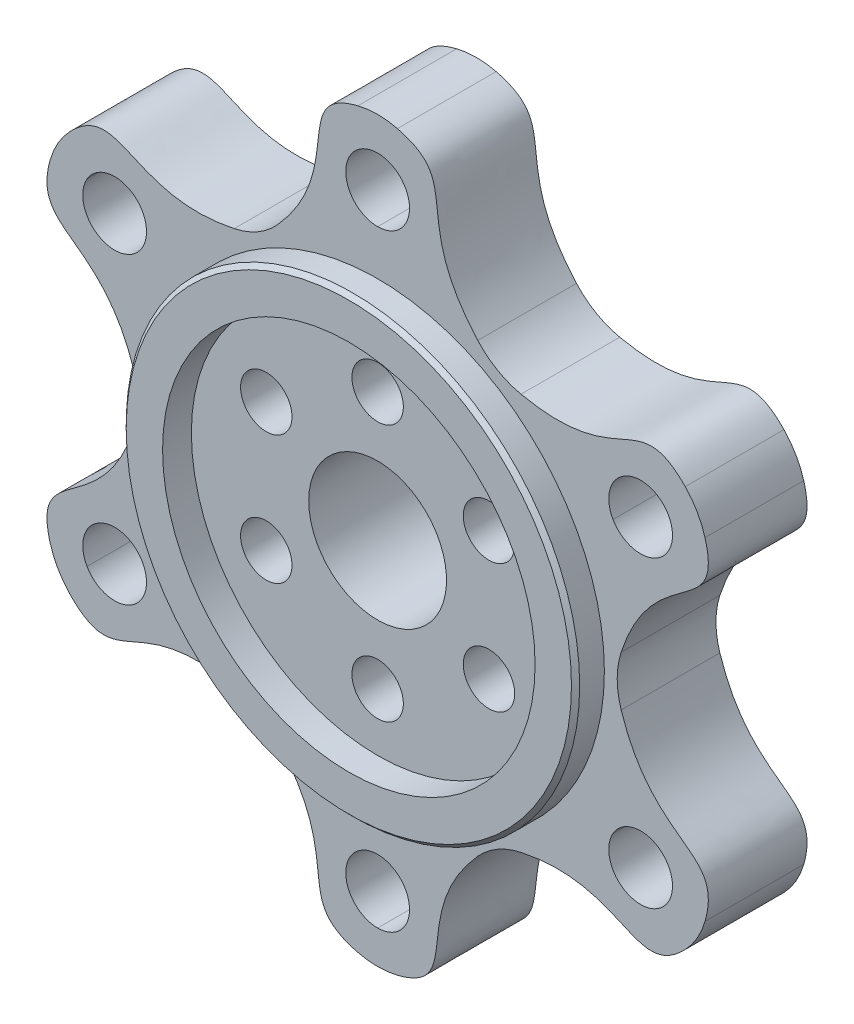
SolidWorks part; units mm, degrees
ref_plane "Front Plane" through (0, 0, 0) normal (0, 0, 1) x (1, 0, 0)
ref_plane "Top Plane" through (0, 0, 0) normal (0, 1, 0) x (1, 0, 0)
ref_plane "Right Plane" through (0, 0, 0) normal (1, 0, 0) x (0, 0, -1)
sketch "Sketch1" plane through (0, 0, 0) normal (0, 0, 1) x (1, 0, 0)
  line L0 (0, -55) -> (0, 55) construction
  line L1 (0, 0) -> (0, 45.72) construction
  circle A0 centre (0, 0) radius 8.509
  circle A1 centre (0, 0) radius 45.72
  circle A2 centre (0, 15.875) radius 3.175
  circle A3 centre (13.7482, 7.9375) radius 3.175
  circle A4 centre (13.7482, -7.9375) radius 3.175
  circle A5 centre (0, -15.875) radius 3.175
  circle A6 centre (-13.7482, -7.9375) radius 3.175
  circle A7 centre (-13.7482, 7.9375) radius 3.175
  circle A8 centre (0, 37.5) radius 3.937
  circle A10 centre (32.476, 18.75) radius 3.937
  circle A11 centre (32.476, -18.75) radius 3.937
  circle A12 centre (0, -37.5) radius 3.937
  circle A13 centre (-32.476, -18.75) radius 3.937
  circle A14 centre (-32.476, 18.75) radius 3.937
  point P21 (0, 0)
  point P36 (0, 0)
  dimension "D1" = 17.018
  dimension "D2" = 91.44
  dimension "D3" = 6.35
  dimension "D6" = 7.874
  dimension "D4" = 15.875
  dimension "D8" = 37.5
  dimension "D5" = 6
  dimension "D7" = 6
extrude "Boss-Extrude3" add sketch "Sketch1" along normal blind 12.192
sketch "Sketch2" plane through (0, 0, 12.192) normal (0, 0, 1) x (1, 0, 0)
  line L0 (0, -55) -> (0, 55) construction
  line L1 (-32.476, 18.75) -> (0, 37.5) construction
  line L2 (-16.238, 28.125) -> (-4.2545, 7.369) construction
  line L3 (16.1981, 28.148) -> (4.2146, 7.3919) construction
  line L6 (32.476, -18.75) -> (32.476, 18.75) construction
  line L7 (32.476, 18.75) -> (0, 37.5) construction
  line L8 (55, 0) -> (-55, 0) construction
  circle A0 centre (0, 0) radius 27.94 construction
  circle A1 centre (0, 0) radius 45.72 construction
  circle A2 centre (0, 0) radius 8.509 construction
  circle A3 centre (0, 0) radius 45.72
  spline S0 degree 3 poles (-14.625, 25.3312) (-1.5745, 37.1177) (-13.1193, 43.9586) (0, 45.72) knots 0 0 0 0 1 1 1 1
  spline S1 degree 3 poles (14.625, 25.3312) (1.5745, 37.1177) (13.1193, 43.9586) (0, 45.72) knots 0 0 0 0 1 1 1 1
  spline S2 degree 3 poles (-29.25, 0) (-32.9321, 17.1953) (-44.6289, 10.6177) (-39.5947, 22.86) knots 0 0 0 0 1 1 1 1
  spline S3 degree 3 poles (-14.625, 25.3312) (-31.3576, 19.9224) (-31.5096, 33.3409) (-39.5947, 22.86) knots 0 0 0 0 1 1 1 1
  spline S4 degree 3 poles (-14.625, -25.3312) (-31.3576, -19.9224) (-31.5096, -33.3409) (-39.5947, -22.86) knots 0 0 0 0 1 1 1 1
  spline S5 degree 3 poles (-29.25, 0) (-32.9321, -17.1953) (-44.6289, -10.6177) (-39.5947, -22.86) knots 0 0 0 0 1 1 1 1
  spline S6 degree 3 poles (14.625, -25.3312) (31.3576, -19.9224) (31.5096, -33.3409) (39.5947, -22.86) knots 0 0 0 0 1 1 1 1
  spline S7 degree 3 poles (29.25, 0) (32.9321, -17.1953) (44.6289, -10.6177) (39.5947, -22.86) knots 0 0 0 0 1 1 1 1
  spline S8 degree 3 poles (14.625, -25.3312) (1.5745, -37.1177) (13.1193, -43.9586) (0, -45.72) knots 0 0 0 0 1 1 1 1
  spline S9 degree 3 poles (-14.625, -25.3312) (-1.5745, -37.1177) (-13.1193, -43.9586) (0, -45.72) knots 0 0 0 0 1 1 1 1
  spline S10 degree 3 poles (29.25, 0) (32.9321, 17.1953) (44.6289, 10.6177) (39.5947, 22.86) knots 0 0 0 0 1 1 1 1
  spline S11 degree 3 poles (14.625, 25.3312) (31.3576, 19.9224) (31.5096, 33.3409) (39.5947, 22.86) knots 0 0 0 0 1 1 1 1
  point P5 (-16.238, 28.125)
  point P6 (16.1981, 28.148)
  circle M8 centre (0, 0) radius 45.72
  dimension "D1" = 55.88
  dimension "D2" = 18.796
  dimension "D3" = 29.25
extrude "Cut-Extrude1" cut sketch "Sketch2" against normal blind 22.86 contours S1 S11 M8 | S5 S2 A3 | S10 S7 A3 | S6 S8 A3 | S9 S4 M8 | S3 S0 M8 region at (38.672, 0, 12.192) region at (19.336, 33.4909, 12.192) region at (19.336, -33.4909, 12.192) region at (-19.336, 33.4909, 12.192) region at (-19.336, -33.4909, 12.192) region at (-38.672, 0, 12.192)
sketch "Sketch4" plane through (0, 0, 12.192) normal (0, 0, 1) x (1, 0, 0)
  circle A0 centre (0, 0) radius 8.509 construction
  circle A1 centre (0, 0) radius 8.509 construction
  circle A2 centre (0, 0) radius 28
  circle A3 centre (0, 0) radius 23
  dimension "D1" = 56
  dimension "D2" = 46
extrude "Boss-Extrude4" add sketch "Sketch4" along normal blind 3.556 contours A2 | A3
ref_plane "Plane1" through (0, 0, 0) normal (1, 0, 0) x (0, 0, -1)
ref_plane "Plane2" through (0, 0, 0) normal (-0.5, -0.866, 0) x (-0.866, 0.5, 0)
ref_plane "Plane3" through (0, 0, 0) normal (-0.5, 0.866, 0) x (0.866, 0.5, 0)
split line "Split Line1"
split line "Split Line2"
split line "Split Line3"
ref_axis "Axis1" through (0, 0, 12.192) along (0, 0, -1)
fillet "Fillet1" radius 10 12 edges at (29.25, 0, 6.096) (39.5947, -22.86, 6.096) (0, -45.72, 6.096) (14.625, -25.3312, 6.096) (-14.625, -25.3312, 6.096) (-39.5947, -22.86, 6.096) (-29.25, 0, 6.096) (-39.5947, 22.86, 6.096) (-14.625, 25.3312, 6.096) (14.625, 25.3312, 6.096) (39.5947, 22.86, 6.096) (0, 45.72, 6.096)
chamfer "Chamfer1" distance 0.508 angle 45 1 edges at (28, 0, 15.748)
